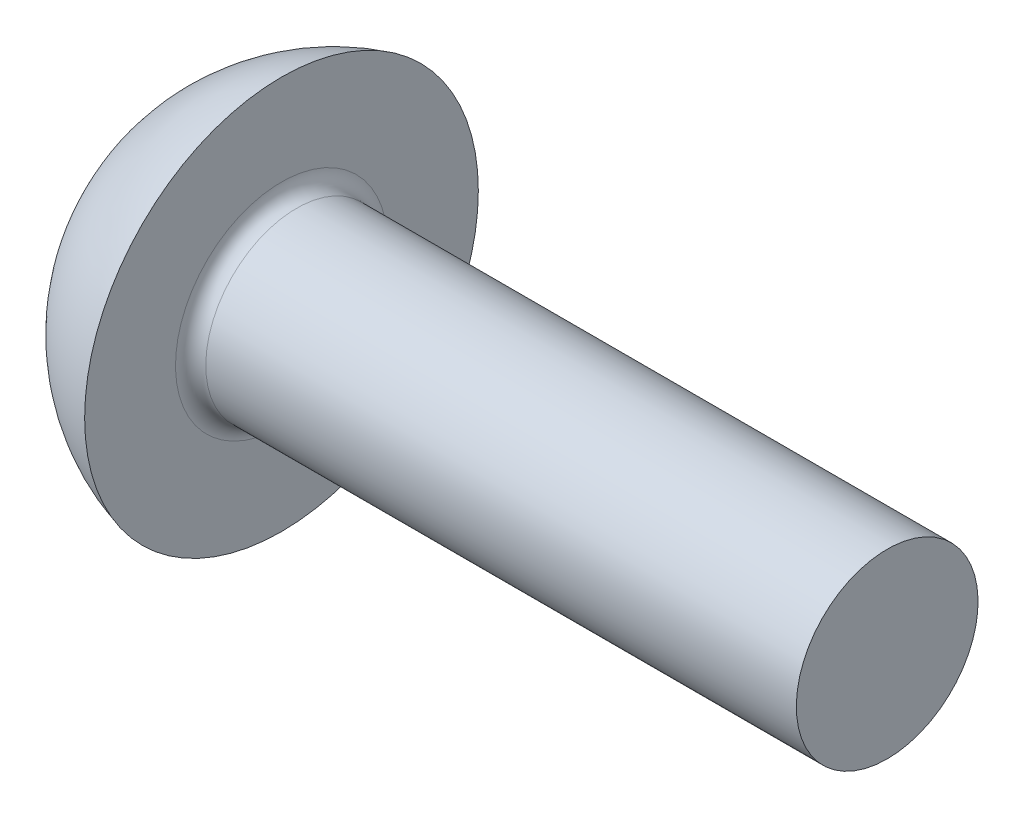
SolidWorks part; units mm, degrees
ref_plane "Front" through (0, 0, 0) normal (0, 0, 1) x (1, 0, 0)
ref_plane "Top" through (0, 0, 0) normal (0, 1, 0) x (1, 0, 0)
ref_plane "Right" through (0, 0, 0) normal (1, 0, 0) x (0, 0, -1)
sketch "Sketch1" plane through (3.1034, 2.4534, 0) normal (0, 0, 1) x (0, 1, 0)
  line L0 (-2.4534, 0.6034) -> (-2.4534, 3.1034)
  line L1 (-1.8034, 2.6034) -> (-2.1534, 2.6034)
  line L2 (-2.1534, 2.6034) -> (-2.1534, 0.6034)
  line L3 (-2.4534, 0.6034) -> (-2.1534, 0.6034)
  line L4 (-2.4534, 7.0931) -> (-2.4534, -0.3296) construction
  arc A0 (-2.4534, 3.1034) -> (-1.8034, 2.6034) centre (-2.4534, 2.4309) cw
  dimension "l" = 2
  dimension "K" = 0.5
  dimension "d" = 0.6
  dimension "dk" = 1.3
revolve "Base-Revolve" add sketch "Sketch1" angle 360 about L4
fillet "Fillet1" radius 0.05 1 edges at (0.5, -0.3, 0)
